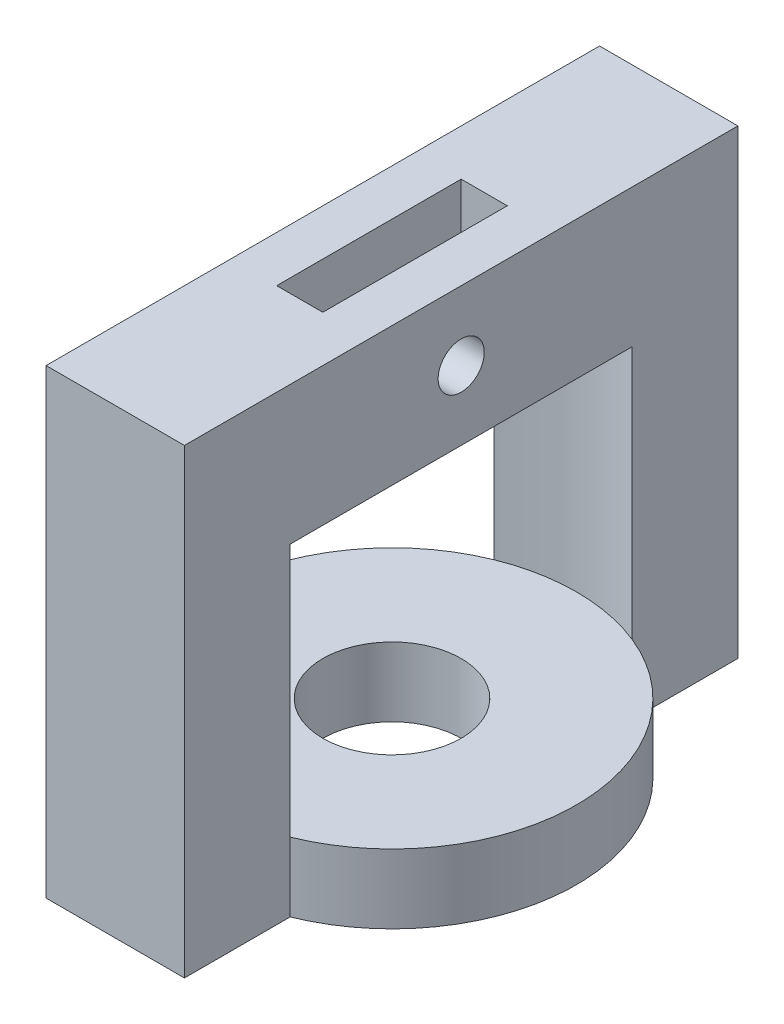
SolidWorks part; units mm, degrees
ref_plane "Front Plane" through (0, 0, 0) normal (0, 0, 1) x (1, 0, 0)
ref_plane "Top Plane" through (0, 0, 0) normal (0, 1, 0) x (1, 0, 0)
ref_plane "Right Plane" through (0, 0, 0) normal (1, 0, 0) x (0, 0, -1)
sketch "Sketch1" plane through (0, 0, 0) normal (0, 1, 0) x (1, 0, 0)
  circle A0 centre (0, 0) radius 4
  circle A1 centre (0, 0) radius 1.5
extrude "Boss-Extrude1" add sketch "Sketch1" along normal blind 1.5
sketch "Sketch2" plane through (0, 1.5, 0) normal (0, 1, 0) x (1, 0, 0)
  line L1 (3.1754, 0) -> (1.5877, 2.75)
  line L2 (1.5877, 2.75) -> (-1.5877, 2.75)
  line L3 (-1.5877, 2.75) -> (-3.1754, 0)
  line L4 (-3.1754, 0) -> (-1.5877, -2.75)
  line L5 (-1.5877, -2.75) -> (1.5877, -2.75)
  line L6 (1.5877, -2.75) -> (3.1754, 0)
  circle A0 centre (0, 0) radius 2.75 construction
  dimension "D1" = 5.5
sketch "Sketch3" plane through (0, 0, 0) normal (0, 1, 0) x (1, 0, 0)
  line L0 (-1.5, -3.7081) -> (-1.5, -6)
  line L1 (-1.5, 6) -> (1.5, 6)
  line L2 (-1.5, 6) -> (-1.5, 3.7081)
  line L3 (-1.5, -6) -> (1.5, -6)
  line L4 (1.5, 6) -> (1.5, 3.7081)
  line L5 (-1.5, 6) -> (1.5, -6) construction
  line L6 (-1.5, -6) -> (1.5, 6) construction
  line L7 (1.5, -3.7081) -> (1.5, -6)
  circle A0 centre (0, 0) radius 4 construction
  arc A1 (-1.5, 3.7081) -> (1.5, 3.7081) centre (0, 0) cw
  arc A2 (-1.5, -3.7081) -> (1.5, -3.7081) centre (0, 0) ccw
  point P0 (0, 0)
  dimension "D1" = 6
  dimension "D2" = 3
extrude "Boss-Extrude2" add sketch "Sketch3" along normal blind 7
sketch "Sketch4" plane through (0, 7, 0) normal (0, 1, 0) x (1, 0, 0)
  line L1 (-1.5, 6) -> (1.5, 6)
  line L2 (-1.5, 6) -> (-1.5, -6)
  line L3 (-1.5, -6) -> (1.5, -6)
  line L4 (1.5, 6) -> (1.5, -6)
extrude "Boss-Extrude3" add sketch "Sketch4" along normal blind 3
sketch "Sketch5" plane through (0, 10, 0) normal (0, 1, 0) x (1, 0, 0)
  line L1 (-0.5, 2) -> (0.5, 2)
  line L2 (-0.5, 2) -> (-0.5, -2)
  line L3 (-0.5, -2) -> (0.5, -2)
  line L4 (0.5, 2) -> (0.5, -2)
  line L5 (-0.5, 2) -> (0.5, -2) construction
  line L6 (-0.5, -2) -> (0.5, 2) construction
  point P0 (0, 0)
  dimension "D1" = 1
  dimension "D2" = 4
extrude "Cut-Extrude1" cut sketch "Sketch5" against normal up to next
sketch "Sketch6" plane through (-1.5, 0, 0) normal (-1, 0, 0) x (0, 0, 1)
  line L0 (0, 10) -> (0, 7) construction
  line L1 (-6, 10) -> (6, 10) construction
  line L2 (-3.7081, 7) -> (3.7081, 7) construction
  circle A0 centre (0, 8.5) radius 0.5
  dimension "D1" = 1
extrude "Cut-Extrude2" cut sketch "Sketch6" against normal through all
